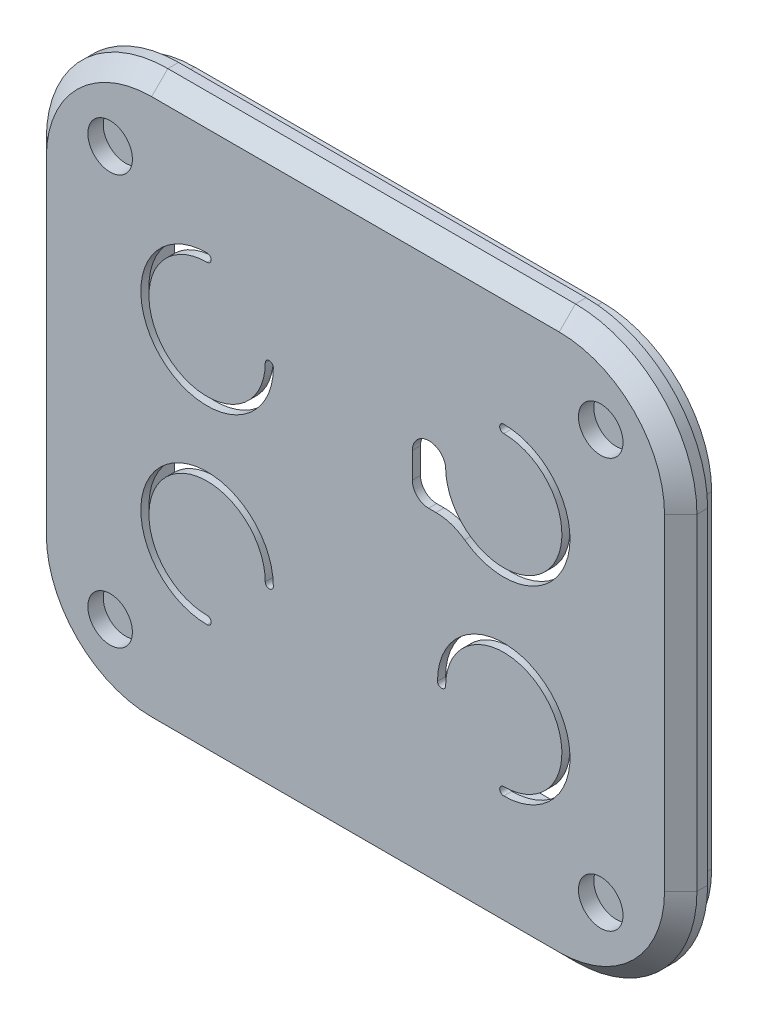
SolidWorks part; units mm, degrees
ref_plane "Plan de face" through (0, 0, 0) normal (0, 0, 1) x (1, 0, 0)
ref_plane "Plan de dessus" through (0, 0, 0) normal (0, 1, 0) x (1, 0, 0)
ref_plane "Plan de droite" through (0, 0, 0) normal (1, 0, 0) x (0, 0, -1)
sketch "Esquisse1" plane through (0, 0, 0) normal (0, 0, 1) x (1, 0, 0)
  line L0 (10, 20) -> (24.0876, 5.9124) construction
  line L1 (30.15, -20.15) -> (30.15, 20.15) construction
  line L2 (-25.15, -25.15) -> (25.15, -25.15) construction
  line L3 (-30.15, 20.15) -> (-30.15, -20.15) construction
  line L4 (25.15, 25.15) -> (-25.15, 25.15) construction
  line L5 (30.15, -20.15) -> (30.15, 20.15) construction
  line L6 (-25.15, -25.15) -> (25.15, -25.15) construction
  line L7 (-30.15, 20.15) -> (-30.15, -20.15) construction
  line L8 (25.15, 25.15) -> (-25.15, 25.15) construction
  line L9 (25.15, 35.15) -> (-25.15, 35.15)
  line L10 (-40.15, 20.15) -> (-40.15, -20.15)
  line L11 (-25.15, -35.15) -> (25.15, -35.15)
  line L12 (40.15, -20.15) -> (40.15, 20.15)
  line L17 (11.1305, 11.6936) -> (11.1305, 18.8695) construction
  line L18 (7.0241, 8.2466) -> (7.0241, 11.4217)
  line L19 (-27.65, 20.15) -> (-27.65, -20.15)
  line L20 (-25.15, -22.65) -> (25.15, -22.65)
  line L21 (27.65, -20.15) -> (27.65, 20.15)
  line L22 (25.15, 22.65) -> (-25.15, 22.65)
  line L23 (0, -55) -> (0, 55) construction
  line L24 (55, 0) -> (-55, 0) construction
  line L25 (18.3064, 18.8695) -> (11.1305, 18.8695) construction
  line L26 (9.0241, 6.2466) -> (9.9444, 6.2466)
  arc A0 (11.1305, 11.6936) -> (18.3064, 18.8695) centre (18.3064, 11.6936) ccw
  arc A1 (13.4836, 5.0916) -> (18.3064, 19.8695) centre (18.3064, 11.6936) ccw
  arc A2 (11.1305, 11.6936) -> (10.1305, 11.6936) centre (10.6305, 11.6936) ccw
  arc A3 (30.15, 20.15) -> (25.15, 25.15) centre (25.15, 20.15) ccw construction
  arc A4 (25.15, -25.15) -> (30.15, -20.15) centre (25.15, -20.15) ccw construction
  arc A5 (-30.15, -20.15) -> (-25.15, -25.15) centre (-25.15, -20.15) ccw construction
  arc A6 (-25.15, 25.15) -> (-30.15, 20.15) centre (-25.15, 20.15) ccw construction
  arc A7 (30.15, 20.15) -> (25.15, 25.15) centre (25.15, 20.15) ccw construction
  arc A8 (25.15, -25.15) -> (30.15, -20.15) centre (25.15, -20.15) ccw construction
  arc A9 (-30.15, -20.15) -> (-25.15, -25.15) centre (-25.15, -20.15) ccw construction
  arc A10 (-25.15, 25.15) -> (-30.15, 20.15) centre (-25.15, 20.15) ccw construction
  arc A11 (-25.15, 35.15) -> (-40.15, 20.15) centre (-25.15, 20.15) ccw
  arc A12 (-40.15, -20.15) -> (-25.15, -35.15) centre (-25.15, -20.15) ccw
  arc A13 (25.15, -35.15) -> (40.15, -20.15) centre (25.15, -20.15) ccw
  arc A14 (40.15, 20.15) -> (25.15, 35.15) centre (25.15, 20.15) ccw
  arc A19 (18.3064, 19.8695) -> (18.3064, 18.8695) centre (18.3064, 19.3695) ccw
  arc A20 (-27.65, -20.15) -> (-25.15, -22.65) centre (-25.15, -20.15) ccw
  arc A21 (25.15, -22.65) -> (27.65, -20.15) centre (25.15, -20.15) ccw
  arc A22 (27.65, 20.15) -> (25.15, 22.65) centre (25.15, 20.15) ccw
  arc A23 (-25.15, 22.65) -> (-27.65, 20.15) centre (-25.15, 20.15) ccw
  arc A24 (-11.1305, 11.6936) -> (-10.1305, 11.6936) centre (-10.6305, 11.6936) cw
  arc A25 (-18.3064, 19.8695) -> (-18.3064, 18.8695) centre (-18.3064, 19.3695) cw
  arc A26 (-11.1305, 11.6936) -> (-18.3064, 18.8695) centre (-18.3064, 11.6936) cw
  arc A27 (-10.1305, 11.6936) -> (-18.3064, 19.8695) centre (-18.3064, 11.6936) cw
  arc A28 (-18.3064, -19.8695) -> (-18.3064, -18.8695) centre (-18.3064, -19.3695) ccw
  arc A29 (-10.1305, -11.6936) -> (-18.3064, -19.8695) centre (-18.3064, -11.6936) ccw
  arc A30 (-11.1305, -11.6936) -> (-10.1305, -11.6936) centre (-10.6305, -11.6936) ccw
  arc A31 (-11.1305, -11.6936) -> (-18.3064, -18.8695) centre (-18.3064, -11.6936) ccw
  arc A32 (10.1305, -11.6936) -> (18.3064, -19.8695) centre (18.3064, -11.6936) cw
  arc A33 (11.1305, -11.6936) -> (10.1305, -11.6936) centre (10.6305, -11.6936) cw
  arc A34 (18.3064, -19.8695) -> (18.3064, -18.8695) centre (18.3064, -19.3695) cw
  arc A35 (11.1305, -11.6936) -> (18.3064, -18.8695) centre (18.3064, -11.6936) cw
  arc A36 (11.1229, 11.7805) -> (7.0241, 11.4217) centre (9.0892, 11.4217) ccw
  arc A37 (9.0241, 6.2466) -> (7.0241, 8.2466) centre (9.0241, 8.2466) cw
  arc A38 (13.4836, 5.0916) -> (9.9444, 6.2466) centre (9.9444, 0.2466) ccw
  dimension "D1" = 10
  dimension "D2" = 1
  dimension "D3" = 2.5
  dimension "D6" = 2
  dimension "D7" = 6
  dimension "D4" = 2.5
extrude "Flexture" add sketch "Esquisse1" along normal blind 1 contours L12 A14 L9 A11 L10 A12 L11 A13 | A0 A1 | L22 A23 L19 A20 L20 A21 L21 A22 A19 A1 A2 A0 region at (35.0019, 30.0019, 0) region at (-0.0987, -0.1035, 0)
extrude "General" add sketch "Esquisse1<6>" against normal blind 4.32 contours L21 A22 L22 A23 L19 A20 L20 A21 | L9 A11 L10 A12 L11 A13 L12 A14
sketch "Esquisse1<6>" plane through (0, 0, 0) normal (0, 0, 1) x (1, 0, 0) same geometry as "Esquisse1"
chamfer "Chanfrein1" distance 2 angle 45 8 edges at (35.7566, 30.7566, 1) (0, 35.15, 1) (40.15, 0, 1) (-35.7566, 30.7566, 1) (35.7566, -30.7566, 1) (-40.15, 0, 1) (0, -35.15, 1) (-35.7566, -30.7566, 1)
sketch "Esquisse4" plane through (0, 0, -4.32) normal (0, 0, -1) x (-1, 0, 0)
  line L0 (-40.15, -20.15) -> (-40.15, 20.15) construction
  line L1 (-25.15, 35.15) -> (25.15, 35.15) construction
  line L2 (40.15, 20.15) -> (40.15, -20.15) construction
  line L3 (25.15, -35.15) -> (-25.15, -35.15) construction
  line L4 (-40.15, -20.15) -> (-40.15, 20.15)
  line L5 (-25.15, 35.15) -> (25.15, 35.15)
  line L6 (40.15, 20.15) -> (40.15, -20.15)
  line L7 (25.15, -35.15) -> (-25.15, -35.15)
  line L8 (25.15, -33.65) -> (-25.15, -33.65)
  line L9 (-38.65, -20.15) -> (-38.65, 20.15)
  line L10 (-25.15, 33.65) -> (25.15, 33.65)
  line L11 (38.65, 20.15) -> (38.65, -20.15)
  arc A0 (-40.15, -20.15) -> (-25.15, -35.15) centre (-25.15, -20.15) ccw construction
  arc A1 (-25.15, 35.15) -> (-40.15, 20.15) centre (-25.15, 20.15) ccw construction
  arc A2 (40.15, 20.15) -> (25.15, 35.15) centre (25.15, 20.15) ccw construction
  arc A3 (25.15, -35.15) -> (40.15, -20.15) centre (25.15, -20.15) ccw construction
  arc A4 (-40.15, -20.15) -> (-25.15, -35.15) centre (-25.15, -20.15) ccw
  arc A5 (-25.15, 35.15) -> (-40.15, 20.15) centre (-25.15, 20.15) ccw
  arc A6 (40.15, 20.15) -> (25.15, 35.15) centre (25.15, 20.15) ccw
  arc A7 (25.15, -35.15) -> (40.15, -20.15) centre (25.15, -20.15) ccw
  arc A8 (-38.65, -20.15) -> (-25.15, -33.65) centre (-25.15, -20.15) ccw
  arc A9 (-25.15, 33.65) -> (-38.65, 20.15) centre (-25.15, 20.15) ccw
  arc A10 (38.65, 20.15) -> (25.15, 33.65) centre (25.15, 20.15) ccw
  arc A11 (25.15, -33.65) -> (38.65, -20.15) centre (25.15, -20.15) ccw
  dimension "D1" = 1.5
extrude "Enlèv. mat.-Extru.1" cut sketch "Esquisse4" against normal blind 2
sketch "Esquisse2" plane through (0, 0, 0) normal (0, 0, -1) x (-1, 0, 0)
  line L0 (-35.7566, 30.7566) -> (-26.9178, 21.9178) construction
  arc A0 (-25.15, 22.65) -> (-27.65, 20.15) centre (-25.15, 20.15) ccw construction
  arc A2 (-25.15, 22.65) -> (-27.65, 20.15) centre (-25.15, 20.15) ccw construction
  circle A4 centre (-30.2765, 25.2765) radius 1.75
  circle A5 centre (-30.2765, 25.2765) radius 2.75
  arc A7 (-25.15, 35.15) -> (-40.15, 20.15) centre (-25.15, 20.15) ccw construction
  arc A8 (-25.15, 35.15) -> (-40.15, 20.15) centre (-25.15, 20.15) ccw construction
  dimension "D1" = 3.5
  dimension "D2" = 5.5
  dimension "D3" = 2
extrude "Passage vis" cut sketch "Esquisse2" along normal through all contours A4
extrude "Lamage vis" cut sketch "Esquisse2<3>" along normal blind 1.9 from surface contours A5 starting at face at (0, 0, 1)
sketch "Esquisse2<3>" plane through (0, 0, 0) normal (0, 0, -1) x (-1, 0, 0) same geometry as "Esquisse2"
sketch "Esquisse3" plane through (0, 0, -0.9) normal (0, 0, 1) x (1, 0, 0)
  circle A0 centre (30.2765, 25.2765) radius 2.75 construction
  circle A1 centre (30.2765, 25.2765) radius 2.75
extrude "ImpressionBridge" add sketch "Esquisse3" against normal blind 0.4
mirror "Symétrie vis" about plane through (0, 0, 0) normal (1, 0, 0) of "ImpressionBridge", "Passage vis", "Lamage vis"
mirror "Symétrie 2 vis" about plane through (0, 0, 0) normal (0, 1, 0) of "Symétrie vis"
